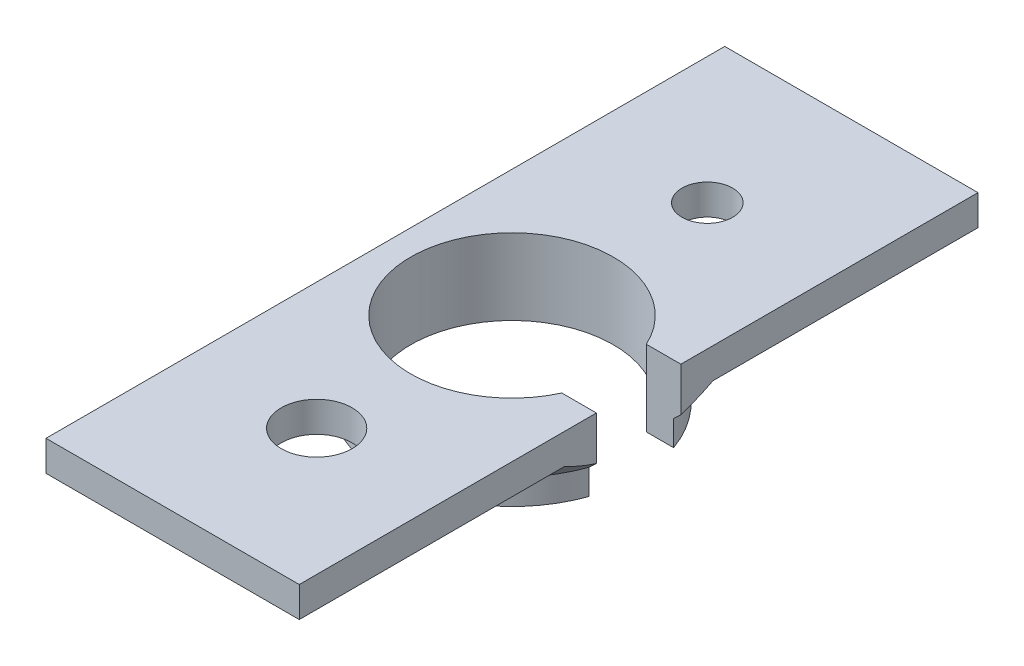
SolidWorks part; units mm, degrees
ref_plane "Спереди" through (0, 0, 0) normal (0, 0, 1) x (1, 0, 0)
ref_plane "Сверху" through (0, 0, 0) normal (0, 1, 0) x (1, 0, 0)
ref_plane "Справа" through (0, 0, 0) normal (1, 0, 0) x (0, 0, -1)
sketch "Эскиз1" plane through (0, 0, 0) normal (0, 1, 0) x (1, 0, 0)
  line L0 (9.0891, -4.17) -> (11.7839, -4.17)
  line L1 (9.0891, 4.17) -> (11.7839, 4.17)
  line L2 (0, 16.9053) -> (0, -20.0169) construction
  line L5 (-18.9959, -4.17) -> (20.7422, -4.17) construction
  line L6 (-18.9959, 0) -> (20.7422, 0) construction
  line L7 (-18.9959, 4.17) -> (20.7422, 4.17) construction
  arc A0 (0, -12.5) -> (11.7839, -4.17) centre (0, 0) ccw
  arc A1 (0, -10) -> (9.0891, -4.17) centre (0, 0) ccw
  arc A4 (11.7839, 4.17) -> (0, -12.5) centre (0, 0) ccw
  arc A5 (9.0891, 4.17) -> (0, -10) centre (0, 0) ccw
  dimension "D1" = 20
  dimension "D2" = 25
  dimension "D4" = 8.34
extrude "Бобышка-Вытянуть1" add sketch "Эскиз1" along normal blind 7.5
sketch "Эскиз2" plane through (0, 7.5, 0) normal (0, 1, 0) x (1, 0, 0)
  line L0 (0, 33.5) -> (0, -20.858) construction
  line L1 (-12.5, -33.5) -> (-12.5, 33.5)
  line L2 (-12.5, 33.5) -> (12.5, 33.5)
  line L3 (-18.8967, 0) -> (22.8149, 0) construction
  line L4 (12.5, -33.5) -> (12.5, -4.17)
  line L5 (-12.5, -33.5) -> (12.5, -33.5)
  line L6 (9.0891, -4.17) -> (12.5, -4.17) construction
  line L7 (9.0891, 4.17) -> (12.5, 4.17)
  line L8 (12.5, 4.17) -> (12.5, 33.5)
  line L9 (9.0891, -4.17) -> (12.5, -4.17)
  circle A0 centre (0, 0) radius 12.5 construction
  circle A1 centre (0, 19.28) radius 2.5
  circle A2 centre (0, -19.28) radius 3.5
  arc A3 (9.0891, 4.17) -> (9.0891, -4.17) centre (0, 0) ccw
  arc A4 (9.0891, 4.17) -> (9.0891, -4.17) centre (0, 0) ccw construction
  point P9 (-12.5, 0)
  point P10 (0, 12.5)
  point P14 (12.5, 0)
  point P15 (-12.5, 0)
  dimension "D4" = 5
  dimension "D5" = 7
  dimension "D1" = 21
  dimension "D2" = 19.28
  dimension "D3" = 19.28
extrude "Бобышка-Вытянуть2" add sketch "Эскиз2" against normal blind 3
chamfer "Фаска1" distance 2 angle 45 2 edges at (-2.1155, 4.5, -12.3197) (-2.1155, 4.5, 12.3197)
